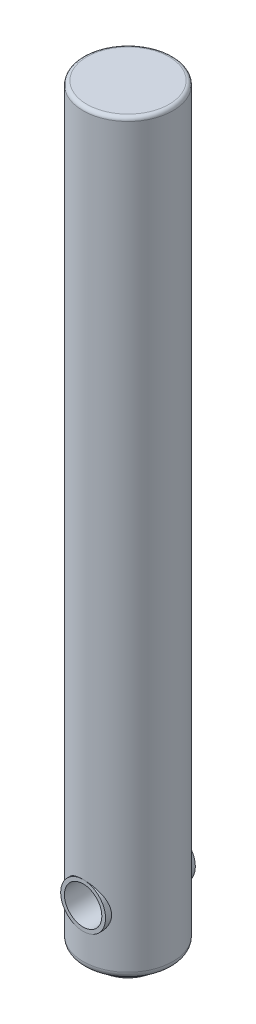
SolidWorks part; units mm, degrees
ref_plane "정면" through (0, 0, 0) normal (0, 0, 1) x (1, 0, 0)
ref_plane "윗면" through (0, 0, 0) normal (0, 1, 0) x (1, 0, 0)
ref_plane "우측면" through (0, 0, 0) normal (1, 0, 0) x (0, 0, -1)
sketch "스케치1" plane through (0, 0, 0) normal (0, 1, 0) x (1, 0, 0)
  circle A0 centre (0, 0) radius 12
  dimension "D1" = 24
extrude "보스-돌출1" add sketch "스케치1" along normal blind 200
ref_plane "평면1" through (0, 0, 12) normal (0, 0, 1) x (1, 0, 0)
sketch "스케치2" plane through (0, 0, 12) normal (0, 0, 1) x (1, 0, 0)
  circle A0 centre (0, 15) radius 6
  dimension "D1" = 12
  dimension "D2" = 15
extrude "보스-돌출2" add sketch "스케치2" against normal through all
sketch "스케치3" plane through (0, 0, 12) normal (0, 0, 1) x (1, 0, 0)
  circle A0 centre (0, 15) radius 5
  dimension "D1" = 10
extrude "컷-돌출1" cut sketch "스케치3" against normal up to next
fillet "필렛1" radius 2 1 edges at (0, 0, 12)
fillet "필렛2" radius 1 1 edges at (0, 200, 12)
dome "돔1" faces to dome 1 distance 5 reverse direction no elliptical dome no face at (0, 0, 10) parameters "D1"=5
